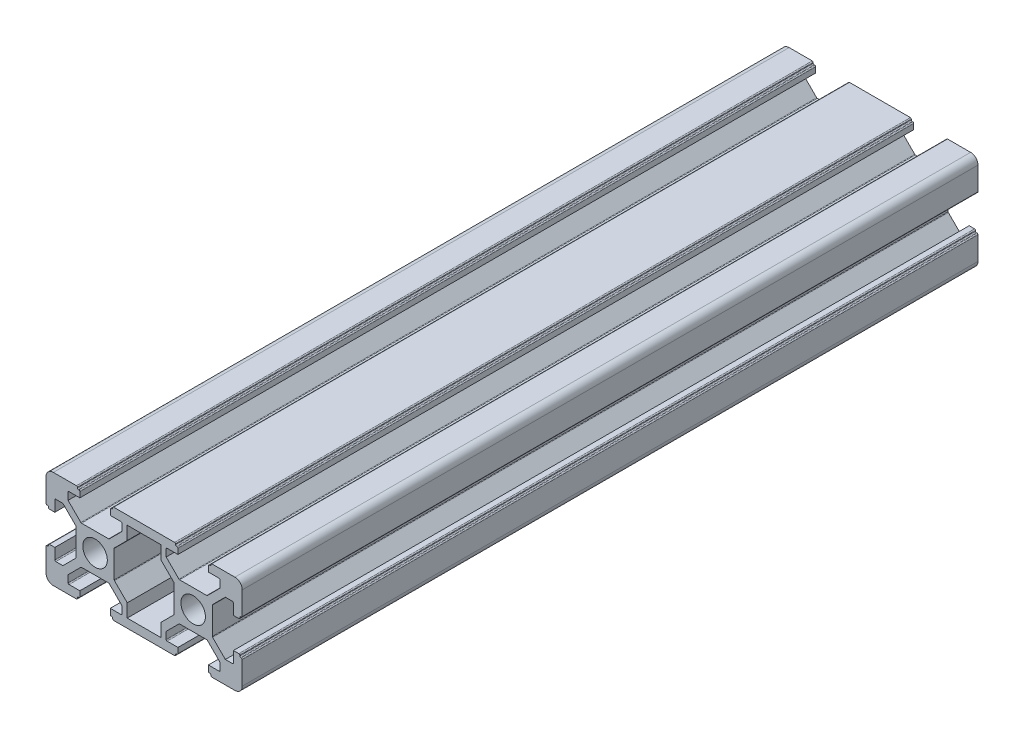
SolidWorks part; units mm, degrees
ref_plane "前视基准面" through (0, 0, 0) normal (0, 0, 1) x (1, 0, 0)
ref_plane "上视基准面" through (0, 0, 0) normal (0, 1, 0) x (1, 0, 0)
ref_plane "右视基准面" through (0, 0, 0) normal (1, 0, 0) x (0, 0, -1)
sketch "Sketch1" plane through (0, 0, 0) normal (0, 0, 1) x (1, 0, 0)
  line L0 (-8.5, 10) -> (-3.8, 10)
  line L3 (-8.5, -10) -> (-3.8, -10)
  line L5 (-10, 8.5) -> (-10, 3.8)
  line L6 (-2.7565, 3.9) -> (2.7565, 3.9)
  line L9 (-2.7565, -3.9) -> (2.7565, -3.9)
  line L10 (3.9, 2.7565) -> (3.9, -2.7565)
  line L11 (-3.9, 2.7565) -> (-3.9, -2.7565)
  line L12 (-3.9586, -2.8979) -> (-6.5607, -5.5)
  line L13 (3.6, 9.7) -> (3.6, 9.8)
  line L14 (3.1, -8.2) -> (5.3, -8.2)
  line L15 (-2.8979, -3.9586) -> (-5.5, -6.5607)
  line L16 (-3.1, -8.2) -> (-3.1, -9.3)
  line L17 (3.1, -8.2) -> (3.1, -9.3)
  line L18 (-5.5, -6.5607) -> (-5.5, -8)
  line L19 (5.5, -6.5607) -> (5.5, -8)
  line L20 (-5.3, -8.2) -> (-3.1, -8.2)
  line L21 (-3.4, -9.5) -> (-3.3, -9.5)
  line L22 (3.8, -10) -> (8.5, -10)
  line L23 (3.3, -9.5) -> (3.4, -9.5)
  line L24 (-3.6, -9.7) -> (-3.6, -9.8)
  line L25 (3.6, -9.7) -> (3.6, -9.8)
  line L26 (-6.5607, -5.5) -> (-8, -5.5)
  line L27 (-9.7, -3.6) -> (-9.8, -3.6)
  line L28 (-9.5, -3.4) -> (-9.5, -3.3)
  line L29 (-8.2, -3.1) -> (-9.3, -3.1)
  line L30 (-8.2, -5.3) -> (-8.2, -3.1)
  line L31 (-10, -3.8) -> (-10, -8.5)
  line L33 (3.8, 10) -> (8.5, 10)
  line L34 (2.8979, -3.9586) -> (5.5, -6.5607)
  line L40 (3.9586, -2.8979) -> (6.5607, -5.5)
  line L41 (3.3, 9.5) -> (3.4, 9.5)
  line L42 (30, 8.5) -> (30, 3.8)
  line L43 (3.1, 8.2) -> (3.1, 9.3)
  line L44 (3.1, 8.2) -> (5.3, 8.2)
  line L45 (5.5, 6.5607) -> (5.5, 8)
  line L46 (2.8979, 3.9586) -> (5.5, 6.5607)
  line L52 (3.9586, 2.8979) -> (6.5607, 5.5)
  line L53 (-3.6, 9.7) -> (-3.6, 9.8)
  line L54 (-3.4, 9.5) -> (-3.3, 9.5)
  line L55 (-3.1, 8.2) -> (-3.1, 9.3)
  line L56 (-5.3, 8.2) -> (-3.1, 8.2)
  line L57 (-5.5, 6.5607) -> (-5.5, 8)
  line L58 (-2.8979, 3.9586) -> (-5.5, 6.5607)
  line L59 (-9.5, 3.4) -> (-9.5, 3.3)
  line L60 (-9.7, 3.6) -> (-9.8, 3.6)
  line L61 (-8.2, 3.1) -> (-9.3, 3.1)
  line L62 (-8.2, 5.3) -> (-8.2, 3.1)
  line L63 (-6.5607, 5.5) -> (-8, 5.5)
  line L64 (-3.9586, 2.8979) -> (-6.5607, 5.5)
  line L65 (29.7, 3.6) -> (29.8, 3.6)
  line L66 (29.5, 3.4) -> (29.5, 3.3)
  line L67 (28.2, 3.1) -> (29.3, 3.1)
  line L68 (28.2, 5.3) -> (28.2, 3.1)
  line L69 (26.5607, 5.5) -> (28, 5.5)
  line L70 (23.9586, 2.8979) -> (26.5607, 5.5)
  line L71 (23.9, 2.7565) -> (23.9, -2.7565)
  line L72 (23.9586, -2.8979) -> (26.5607, -5.5)
  line L73 (26.5607, -5.5) -> (28, -5.5)
  line L74 (28.2, -5.3) -> (28.2, -3.1)
  line L75 (28.2, -3.1) -> (29.3, -3.1)
  line L76 (29.5, -3.4) -> (29.5, -3.3)
  line L77 (29.7, -3.6) -> (29.8, -3.6)
  line L78 (30, -3.8) -> (30, -8.5)
  line L79 (28.5, -10) -> (23.8, -10)
  line L80 (23.6, -9.7) -> (23.6, -9.8)
  line L81 (23.4, -9.5) -> (23.3, -9.5)
  line L82 (23.1, -8.2) -> (23.1, -9.3)
  line L83 (25.3, -8.2) -> (23.1, -8.2)
  line L84 (25.5, -6.5607) -> (25.5, -8)
  line L85 (22.8979, -3.9586) -> (25.5, -6.5607)
  line L86 (22.7565, -3.9) -> (17.2435, -3.9)
  line L87 (17.1021, -3.9586) -> (14.5, -6.5607)
  line L88 (14.5, -6.5607) -> (14.5, -8)
  line L89 (16.9, -8.2) -> (14.7, -8.2)
  line L90 (16.9, -8.2) -> (16.9, -9.3)
  line L91 (16.7, -9.5) -> (16.6, -9.5)
  line L92 (16.4, -9.7) -> (16.4, -9.8)
  line L93 (16.2, -10) -> (11.5, -10)
  line L94 (13.4393, 5.5) -> (13.4393, 8.2)
  line L96 (6.5607, 5.5) -> (6.5607, 8.2)
  line L97 (6.5607, 8.2) -> (13.4393, 8.2)
  line L99 (16.0414, -2.8979) -> (13.4393, -5.5)
  line L100 (16.1, 2.7565) -> (16.1, -2.7565)
  line L101 (16.0414, 2.8979) -> (13.4393, 5.5)
  line L107 (16.2, 10) -> (11.5, 10)
  line L108 (16.4, 9.7) -> (16.4, 9.8)
  line L109 (16.7, 9.5) -> (16.6, 9.5)
  line L110 (16.9, 8.2) -> (16.9, 9.3)
  line L111 (16.9, 8.2) -> (14.7, 8.2)
  line L112 (14.5, 6.5607) -> (14.5, 8)
  line L113 (17.1021, 3.9586) -> (14.5, 6.5607)
  line L114 (22.7565, 3.9) -> (17.2435, 3.9)
  line L115 (22.8979, 3.9586) -> (25.5, 6.5607)
  line L116 (25.5, 6.5607) -> (25.5, 8)
  line L117 (25.3, 8.2) -> (23.1, 8.2)
  line L118 (23.1, 8.2) -> (23.1, 9.3)
  line L119 (23.4, 9.5) -> (23.3, 9.5)
  line L120 (23.6, 9.7) -> (23.6, 9.8)
  line L121 (28.5, 10) -> (23.8, 10)
  line L122 (13.4393, -5.5) -> (13.4393, -8.2)
  line L124 (6.5607, -5.5) -> (6.5607, -8.2)
  line L125 (6.5607, -8.2) -> (13.4393, -8.2)
  line L127 (8.5, 10) -> (11.5, 10)
  line L128 (8.5, -10) -> (11.5, -10)
  arc A3 (-8.5, -10) -> (-10, -8.5) centre (-8.5, -8.5) cw
  arc A4 (-10, 8.5) -> (-8.5, 10) centre (-8.5, 8.5) cw
  arc A5 (3.4, -9.5) -> (3.6, -9.7) centre (3.4, -9.7) cw
  arc A6 (3.8, -10) -> (3.6, -9.8) centre (3.8, -9.8) cw
  arc A7 (3.3, -9.5) -> (3.1, -9.3) centre (3.3, -9.3) cw
  arc A8 (5.3, -8.2) -> (5.5, -8) centre (5.3, -8) ccw
  arc A9 (-3.9, -2.7565) -> (-3.9586, -2.8979) centre (-4.1, -2.7565) cw
  arc A10 (-3.9, 2.7565) -> (-3.9586, 2.8979) centre (-4.1, 2.7565) ccw
  arc A11 (-2.7565, 3.9) -> (-2.8979, 3.9586) centre (-2.7565, 4.1) cw
  arc A12 (2.7565, 3.9) -> (2.8979, 3.9586) centre (2.7565, 4.1) ccw
  arc A13 (3.9586, 2.8979) -> (3.9, 2.7565) centre (4.1, 2.7565) ccw
  arc A14 (3.9, -2.7565) -> (3.9586, -2.8979) centre (4.1, -2.7565) ccw
  arc A15 (-2.8979, -3.9586) -> (-2.7565, -3.9) centre (-2.7565, -4.1) cw
  arc A16 (2.7565, -3.9) -> (2.8979, -3.9586) centre (2.7565, -4.1) cw
  arc A17 (-3.6, -9.8) -> (-3.8, -10) centre (-3.8, -9.8) cw
  arc A18 (-3.3, -9.5) -> (-3.1, -9.3) centre (-3.3, -9.3) ccw
  arc A19 (-3.6, -9.7) -> (-3.4, -9.5) centre (-3.4, -9.7) cw
  arc A20 (-8.2, 5.3) -> (-8, 5.5) centre (-8, 5.3) cw
  arc A23 (-8.2, -5.3) -> (-8, -5.5) centre (-8, -5.3) ccw
  arc A24 (-5.3, -8.2) -> (-5.5, -8) centre (-5.3, -8) cw
  arc A31 (3.1, 9.3) -> (3.3, 9.5) centre (3.3, 9.3) cw
  arc A32 (3.6, 9.8) -> (3.8, 10) centre (3.8, 9.8) cw
  arc A33 (3.6, 9.7) -> (3.4, 9.5) centre (3.4, 9.7) cw
  arc A34 (-3.8, 10) -> (-3.6, 9.8) centre (-3.8, 9.8) cw
  arc A35 (-3.3, 9.5) -> (-3.1, 9.3) centre (-3.3, 9.3) cw
  arc A36 (-3.4, 9.5) -> (-3.6, 9.7) centre (-3.4, 9.7) cw
  arc A37 (5.5, 8) -> (5.3, 8.2) centre (5.3, 8) ccw
  arc A38 (-5.5, 8) -> (-5.3, 8.2) centre (-5.3, 8) cw
  arc A39 (-10, 3.8) -> (-9.8, 3.6) centre (-9.8, 3.8) ccw
  arc A40 (-9.5, 3.3) -> (-9.3, 3.1) centre (-9.3, 3.3) ccw
  arc A41 (-9.7, 3.6) -> (-9.5, 3.4) centre (-9.7, 3.4) cw
  arc A42 (-10, -3.8) -> (-9.8, -3.6) centre (-9.8, -3.8) cw
  arc A43 (-9.5, -3.3) -> (-9.3, -3.1) centre (-9.3, -3.3) cw
  arc A44 (-9.5, -3.4) -> (-9.7, -3.6) centre (-9.7, -3.4) cw
  arc A45 (30, 8.5) -> (28.5, 10) centre (28.5, 8.5) ccw
  arc A46 (30, 3.8) -> (29.8, 3.6) centre (29.8, 3.8) cw
  arc A47 (29.7, 3.6) -> (29.5, 3.4) centre (29.7, 3.4) ccw
  arc A48 (29.5, 3.3) -> (29.3, 3.1) centre (29.3, 3.3) cw
  arc A49 (28.2, 5.3) -> (28, 5.5) centre (28, 5.3) ccw
  arc A50 (23.9, 2.7565) -> (23.9586, 2.8979) centre (24.1, 2.7565) cw
  arc A51 (23.9, -2.7565) -> (23.9586, -2.8979) centre (24.1, -2.7565) ccw
  arc A52 (28.2, -5.3) -> (28, -5.5) centre (28, -5.3) cw
  arc A53 (29.5, -3.3) -> (29.3, -3.1) centre (29.3, -3.3) ccw
  arc A54 (29.5, -3.4) -> (29.7, -3.6) centre (29.7, -3.4) ccw
  arc A55 (30, -3.8) -> (29.8, -3.6) centre (29.8, -3.8) ccw
  arc A56 (28.5, -10) -> (30, -8.5) centre (28.5, -8.5) ccw
  arc A57 (23.6, -9.8) -> (23.8, -10) centre (23.8, -9.8) ccw
  arc A58 (23.6, -9.7) -> (23.4, -9.5) centre (23.4, -9.7) ccw
  arc A59 (23.3, -9.5) -> (23.1, -9.3) centre (23.3, -9.3) cw
  arc A60 (25.3, -8.2) -> (25.5, -8) centre (25.3, -8) ccw
  arc A61 (22.8979, -3.9586) -> (22.7565, -3.9) centre (22.7565, -4.1) ccw
  arc A62 (17.2435, -3.9) -> (17.1021, -3.9586) centre (17.2435, -4.1) ccw
  arc A63 (14.7, -8.2) -> (14.5, -8) centre (14.7, -8) cw
  arc A64 (16.7, -9.5) -> (16.9, -9.3) centre (16.7, -9.3) ccw
  arc A65 (16.6, -9.5) -> (16.4, -9.7) centre (16.6, -9.7) ccw
  arc A66 (16.2, -10) -> (16.4, -9.8) centre (16.2, -9.8) ccw
  arc A72 (16.1, -2.7565) -> (16.0414, -2.8979) centre (15.9, -2.7565) cw
  arc A73 (16.0414, 2.8979) -> (16.1, 2.7565) centre (15.9, 2.7565) cw
  arc A79 (16.4, 9.8) -> (16.2, 10) centre (16.2, 9.8) ccw
  arc A80 (16.4, 9.7) -> (16.6, 9.5) centre (16.6, 9.7) ccw
  arc A81 (16.9, 9.3) -> (16.7, 9.5) centre (16.7, 9.3) ccw
  arc A82 (14.5, 8) -> (14.7, 8.2) centre (14.7, 8) cw
  arc A83 (17.2435, 3.9) -> (17.1021, 3.9586) centre (17.2435, 4.1) cw
  arc A84 (22.7565, 3.9) -> (22.8979, 3.9586) centre (22.7565, 4.1) ccw
  arc A85 (25.5, 8) -> (25.3, 8.2) centre (25.3, 8) ccw
  arc A86 (23.3, 9.5) -> (23.1, 9.3) centre (23.3, 9.3) ccw
  arc A87 (23.4, 9.5) -> (23.6, 9.7) centre (23.4, 9.7) ccw
  arc A88 (23.8, 10) -> (23.6, 9.8) centre (23.8, 9.8) ccw
  point P11 (3.9, 3.9)
  point P19 (3.3697, 4.4303)
  point P20 (-10.6428, -10.6428)
  point P25 (-11.1731, -10.1124)
  point P26 (4.4303, 3.3697)
  point P28 (-10.1124, -11.1731)
  dimension "D3" = 0.2
  dimension "D4" = 0.2
  dimension "D5" = 0.2
  dimension "D8" = 0.2
  dimension "D9" = 0.2
  dimension "D10" = 0.2
  dimension "D6" = 1.8
  dimension "D7" = 0.5
extrude "Boss-Extrude1" add sketch "Sketch1" along normal blind 150
ref_plane "hole" through (0, 0, 150) normal (0, 0, 1) x (1, 0, 0)
sketch "Sketch2" plane through (0, 0, 150) normal (0, 0, 1) x (1, 0, 0)
  circle A0 centre (0, 0) radius 2.5
  circle A1 centre (20, 0) radius 2.5
  dimension "D1" = 5
extrude "Cut-Extrude1" cut sketch "Sketch2" against normal through all
sketch "Sketch4" plane through (0, 3.9, 0) normal (0, 1, 0) x (1, 0, 0)
  line L0 (2.7565, -150) -> (-2.7565, -150) construction
  line L1 (10, -150) -> (10, 0) construction
  line L2 (16.2, -150) -> (3.8, -150) construction
  line L3 (16.2, 0) -> (3.8, 0) construction
  circle A0 centre (0, -133.3) radius 1.5
  circle A1 centre (0, -116.6) radius 1.5
  circle A2 centre (20, -116.6) radius 1.5
  circle A3 centre (20, -133.3) radius 1.5
  point P6 (0, -150)
  dimension "D1" = 0
  dimension "D2" = 0
  dimension "D3" = 16.7
  dimension "D4" = 16.7
  dimension "D5" = 3
  dimension "D6" = 3
extrude "Cut-Extrude3" cut sketch "Sketch4" against normal blind 30
